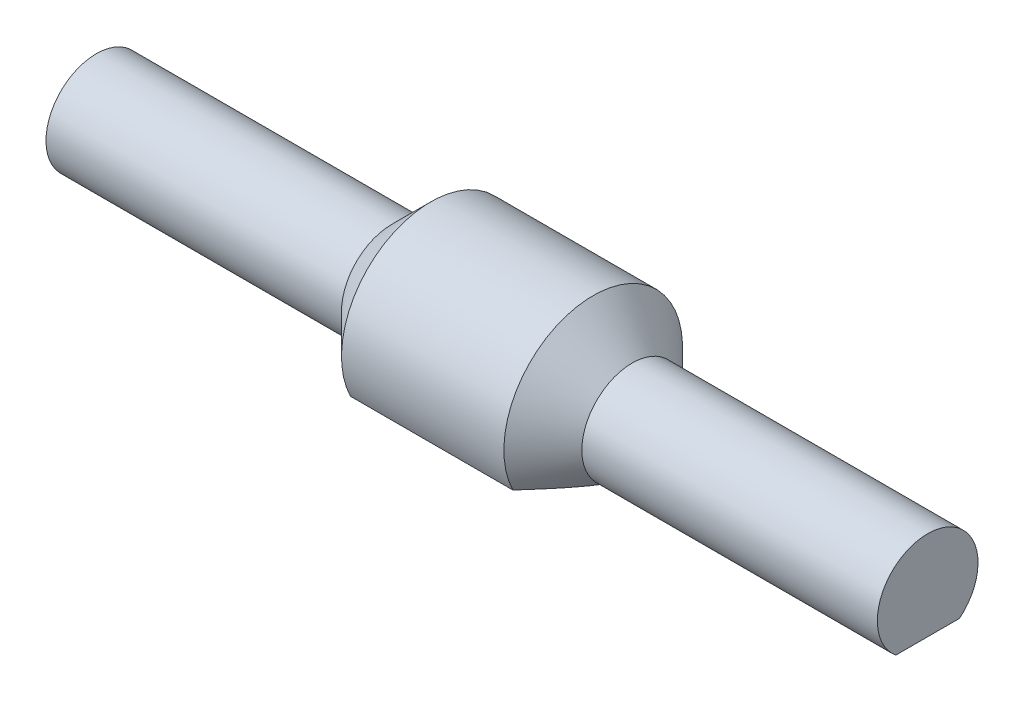
SolidWorks part; units mm, degrees
ref_plane "Front Plane" through (0, 0, 0) normal (0, 0, 1) x (1, 0, 0)
ref_plane "Top Plane" through (0, 0, 0) normal (0, 1, 0) x (1, 0, 0)
ref_plane "Right Plane" through (0, 0, 0) normal (1, 0, 0) x (0, 0, -1)
sketch "Sketch1" plane through (0, 0, 0) normal (0, 0, 1) x (1, 0, 0)
  line L0 (-20, 0) -> (20, 0) construction
  dimension "D1" = 40
sketch "Sketch2" plane through (0, 0, 0) normal (0, 0, 1) x (1, 0, 0)
  line L0 (12.8, 0) -> (12.8, 1.55)
  line L1 (-20, 0) -> (20, 0) construction
  line L2 (12.8, 1.55) -> (3.7, 1.55)
  line L3 (3.7, 1.55) -> (2.5, 2.75)
  line L4 (2.5, 2.75) -> (0, 2.75)
  line L5 (0, 2.75) -> (0, 0)
  line L6 (0, 0) -> (12.8, 0)
  dimension "D1" = 10.3
  dimension "D2" = 2.75
  dimension "D3" = 1.55
  dimension "D4" = 7.2
  dimension "D5" = 45
revolve "Revolve1" add sketch "Sketch2" angle 360 about L0
mirror "Mirror1" about plane through (0, 0, 0) normal (1, 0, 0) of "Revolve1"
sketch "Sketch3" plane through (0, 0, 0) normal (0, 0, 1) x (1, 0, 0)
  line L0 (-12.8, -1.2) -> (12.8, -1.2)
  line L1 (-12.8, 1.55) -> (-12.8, -1.55) construction
  line L2 (12.8, -1.55) -> (12.8, 1.55) construction
  dimension "D1" = 1.2
extrude "Cut-Extrude1" cut sketch "Sketch3" against normal through all both and the other way through all flip side to cut
move or copy body "Body-Move/Copy1" [suppressed] bodies to move or copy 102
move or copy body "Body-Move/Copy2" [suppressed] bodies to move or copy 102
equation "\"end to end\" = 40"
equation "\"D1@Sketch1\"=\"end to end\""
